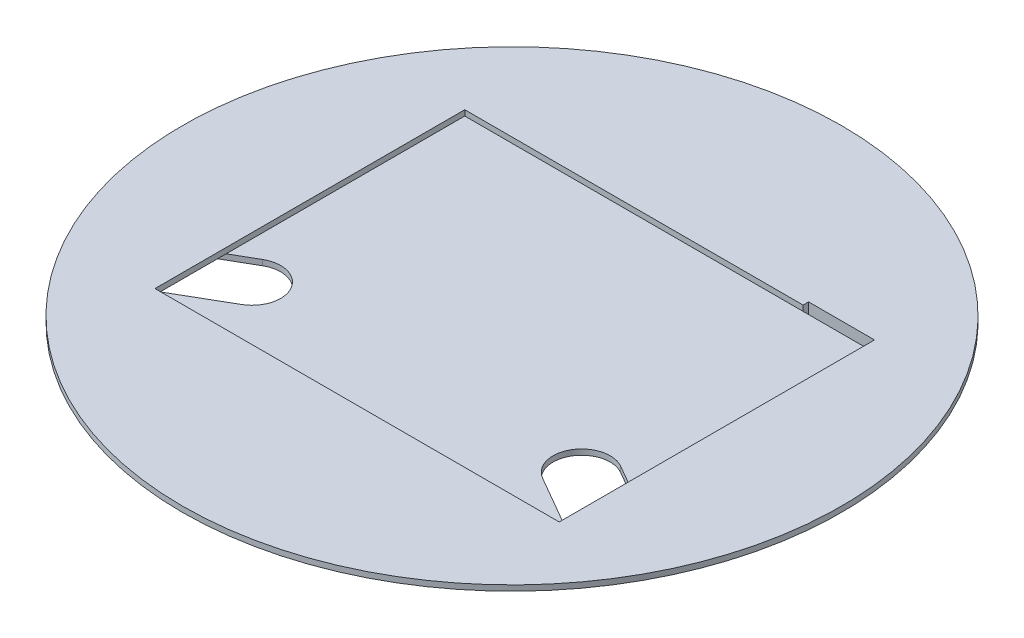
SolidWorks part; units mm, degrees
ref_plane "Front Plane" through (0, 0, 0) normal (0, 0, 1) x (1, 0, 0)
ref_plane "Top Plane" through (0, 0, 0) normal (0, 1, 0) x (1, 0, 0)
ref_plane "Right Plane" through (0, 0, 0) normal (1, 0, 0) x (0, 0, -1)
sketch "Sketch1" plane through (0, 0, 0) normal (0, 1, 0) x (1, 0, 0)
  circle A0 centre (0, 0) radius 150
  dimension "D1" = 300
extrude "Boss-Extrude1" add sketch "Sketch1" along normal blind 5
sketch "Sketch4" plane through (0, 5, 0) normal (0, 1, 0) x (1, 0, 0)
  line L1 (-92, -70.5) -> (92, -70.5)
  line L2 (-92, -70.5) -> (-92, 70.5)
  line L3 (-92, 70.5) -> (92, 70.5)
  line L4 (92, -70.5) -> (92, 70.5)
  line L5 (-92, -70.5) -> (92, 70.5) construction
  line L6 (-92, 70.5) -> (92, -70.5) construction
  point P0 (0, 0)
  dimension "D1" = 184
  dimension "D2" = 141
extrude "Cut-Extrude2" cut sketch "Sketch4" against normal blind 2.5
sketch "Sketch6" plane through (0, 0, 0) normal (0, -1, 0) x (-1, 0, 0)
  line L0 (-13, 86.6003) -> (-13.0054, 118.7171)
  line L1 (-109.3147, -48.0955) -> (-81.4981, -32.0418)
  line L2 (-68.4981, -54.5585) -> (-96.3093, -70.6216)
  line L3 (96.3093, -70.6216) -> (68.4981, -54.5585)
  line L4 (81.4981, -32.0418) -> (109.3147, -48.0955)
  line L5 (13.0054, 118.7171) -> (13, 86.6003)
  line L12 (-12.5, 86.6004) -> (-12.5054, 118.7171) construction
  line L13 (12.5054, 118.7171) -> (12.5, 86.6004) construction
  line L14 (81.2482, -32.4749) -> (109.0648, -48.5285) construction
  line L15 (96.5593, -70.1886) -> (68.7482, -54.1255) construction
  line L16 (-68.7482, -54.1255) -> (-96.5593, -70.1886) construction
  line L17 (-109.0648, -48.5285) -> (-81.2482, -32.4749) construction
  arc A0 (-13.0054, 118.7171) -> (-18.1619, 123.1682) centre (-17.5054, 118.7163) ccw
  arc A1 (-18.1619, 123.1682) -> (-115.7477, -45.8554) centre (0, 0) ccw
  circle A2 centre (0, 0) radius 150
  arc A3 (-115.7477, -45.8554) -> (-109.3147, -48.0955) centre (-111.5641, -44.198) ccw
  arc A4 (-68.4981, -54.5585) -> (-81.4981, -32.0418) centre (-75, -43.3013) ccw
  arc A5 (-96.3093, -70.6216) -> (-97.5858, -77.3127) centre (-94.0586, -74.5183) ccw
  arc A6 (-97.5858, -77.3127) -> (97.5858, -77.3127) centre (0, 0) ccw
  arc A7 (97.5858, -77.3127) -> (96.3093, -70.6216) centre (94.0586, -74.5183) ccw
  arc A8 (81.4981, -32.0418) -> (68.4981, -54.5585) centre (75, -43.3013) ccw
  arc A9 (109.3147, -48.0955) -> (115.7477, -45.8554) centre (111.5641, -44.198) ccw
  arc A10 (115.7477, -45.8554) -> (18.1619, 123.1682) centre (0, 0) ccw
  arc A11 (18.1619, 123.1682) -> (13.0054, 118.7171) centre (17.5054, 118.7163) ccw
  arc A12 (-13, 86.6003) -> (13, 86.6003) centre (0, 86.6025) ccw
  arc A26 (-12.5, 86.6004) -> (12.5, 86.6004) centre (0, 86.6025) ccw construction
  arc A27 (18.2348, 123.6628) -> (12.5054, 118.7171) centre (17.5054, 118.7163) ccw construction
  arc A28 (116.2126, -46.0396) -> (18.2348, 123.6628) centre (0, 0) ccw construction
  arc A29 (109.0648, -48.5285) -> (116.2126, -46.0396) centre (111.5641, -44.198) ccw construction
  arc A30 (81.2482, -32.4749) -> (68.7482, -54.1255) centre (75, -43.3013) ccw construction
  arc A31 (97.9777, -77.6232) -> (96.5593, -70.1886) centre (94.0586, -74.5183) ccw construction
  arc A32 (-97.9777, -77.6232) -> (97.9777, -77.6232) centre (0, 0) ccw construction
  arc A33 (-96.5593, -70.1886) -> (-97.9777, -77.6232) centre (-94.0586, -74.5183) ccw construction
  arc A34 (-68.7482, -54.1255) -> (-81.2482, -32.4749) centre (-75, -43.3013) ccw construction
  arc A35 (-116.2126, -46.0396) -> (-109.0648, -48.5285) centre (-111.5641, -44.198) ccw construction
  arc A36 (-18.2348, 123.6628) -> (-116.2126, -46.0396) centre (0, 0) ccw construction
  arc A37 (-12.5054, 118.7171) -> (-18.2348, 123.6628) centre (-17.5054, 118.7163) ccw construction
  dimension "D1" = 0.5
extrude "Cut-Extrude3" cut sketch "Sketch6" against normal blind 2.5
sketch "Sketch9" plane through (0, 5, 0) normal (0, 1, 0) x (1, 0, 0)
  line L0 (92, 70.5) -> (-92, 70.5) construction
  line L1 (62, 70.5) -> (92, 70.5)
  line L2 (62, 70.5) -> (62, 73)
  line L3 (62, 73) -> (92, 73)
  line L4 (92, 70.5) -> (92, 73)
  line L5 (92, -38.1027) -> (92, 70.5) construction
  line L6 (92, -70.5) -> (92, 70.5) construction
  dimension "D1" = 2.5
  dimension "D2" = 30
  dimension "D3" = 0
extrude "Cut-Extrude10" cut sketch "Sketch9" against normal blind 2.5
sketch "Sketch10" plane through (0, 0, 0) normal (0, -1, 0) x (1, 0, 0)
  line L1 (62, -70.5) -> (92, -70.5)
  line L2 (62, -70.5) -> (62, -73)
  line L3 (62, -73) -> (92, -73)
  line L4 (92, -70.5) -> (92, -73)
  line L14 (92, 38.1027) -> (81.4981, 32.0418)
  line L15 (92, -73) -> (92, 38.1027)
  line L18 (62, -73) -> (92, -73)
  line L19 (62, -70.5) -> (62, -73)
  line L21 (-92, 38.1027) -> (-92, -70.5)
  line L22 (-81.4981, 32.0418) -> (-92, 38.1027)
  line L23 (-92, 68.1326) -> (-68.4981, 54.5585)
  line L24 (-92, -70.5) -> (62, -70.5)
  line L25 (92, 70.5) -> (-92, 70.5)
  line L26 (-92, -70.5) -> (62, -70.5)
  line L27 (68.4981, 54.5585) -> (92, 68.1326)
  line L28 (92, 38.1027) -> (81.4981, 32.0418) construction
  line L29 (92, -73) -> (92, 38.1027) construction
  line L35 (-92, 38.1027) -> (-92, -70.5) construction
  line L36 (-81.4981, 32.0418) -> (-92, 38.1027) construction
  line L37 (-92, 68.1326) -> (-68.4981, 54.5585) construction
  line L39 (92, 70.5) -> (-92, 70.5) construction
  line L41 (68.4981, 54.5585) -> (92, 68.1326) construction
  line L42 (-92, 70.5) -> (-92, 68.1326)
  line L43 (-92, 70.5) -> (-92, 68.1326)
  line L45 (92, 68.1326) -> (92, 70.5)
  line L46 (92, 68.1326) -> (92, 70.5)
  arc A2 (-81.4981, 32.0418) -> (-68.4981, 54.5585) centre (-75, 43.3013) ccw
  arc A3 (68.4981, 54.5585) -> (81.4981, 32.0418) centre (75, 43.3013) ccw
  arc A4 (-81.4981, 32.0418) -> (-68.4981, 54.5585) centre (-75, 43.3013) ccw construction
  arc A5 (68.4981, 54.5585) -> (81.4981, 32.0418) centre (75, 43.3013) ccw construction
  dimension "D2" = 2.5
  dimension "D1" = 0
extrude "Cut-Extrude11" cut sketch "Sketch10" against normal blind 2.5 contours L2 L1 L4 L3
